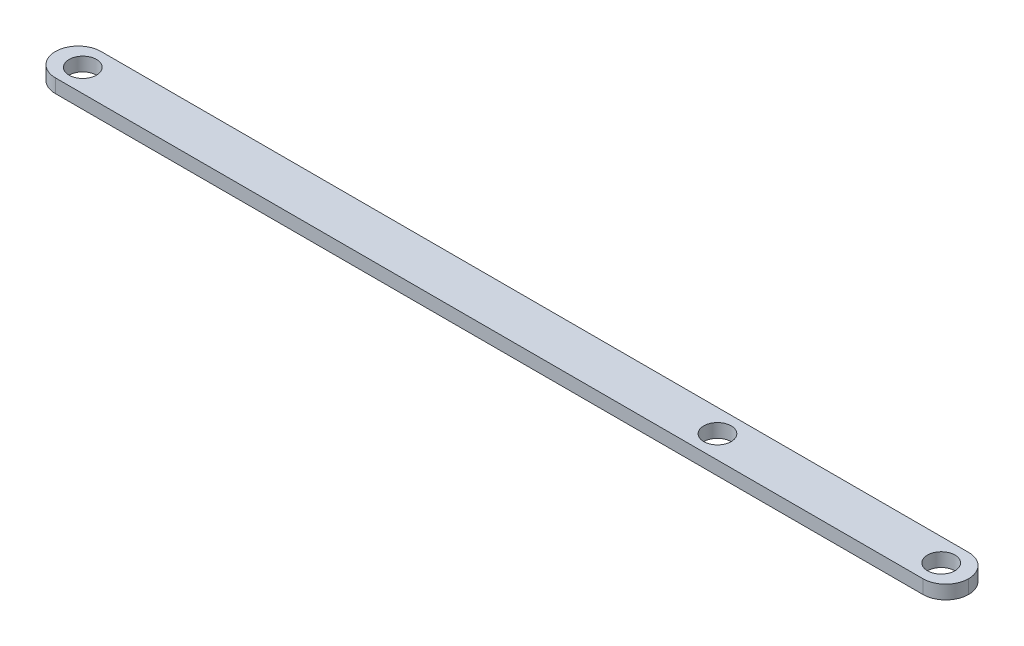
SolidWorks part; units mm, degrees
ref_plane "Front Plane" through (0, 0, 0) normal (0, 0, 1) x (1, 0, 0)
ref_plane "Top Plane" through (0, 0, 0) normal (0, 1, 0) x (1, 0, 0)
ref_plane "Right Plane" through (0, 0, 0) normal (1, 0, 0) x (0, 0, -1)
sketch "Sketch2" plane through (0, 0, 0) normal (0, 1, 0) x (1, 0, 0)
  line L1 (0, 0) -> (200, 0)
  line L2 (0, 0) -> (0, 10)
  line L3 (0, 10) -> (200, 10)
  line L4 (200, 0) -> (200, 10)
  dimension "D1" = 200
  dimension "D2" = 10
extrude "Boss-Extrude1" add sketch "Sketch2" along normal blind 3
sketch "Sketch3" plane through (0, 3, 0) normal (0, 1, 0) x (1, 0, 0)
  line L0 (200, 10) -> (0, 10) construction
  line L1 (0, 10) -> (0, 0) construction
  circle A0 centre (6, 5) radius 3
  dimension "D1" = 5
  dimension "D2" = 6
  dimension "D3" = 6
extrude "Cut-Extrude1" cut sketch "Sketch3" against normal through all
sketch "Sketch4" plane through (0, 3, 0) normal (0, 1, 0) x (1, 0, 0)
  line L0 (200, 10) -> (0, 10) construction
  line L1 (200, 0) -> (200, 10) construction
  circle A0 centre (194, 5) radius 3
  dimension "D1" = 5
  dimension "D3" = 6
  dimension "D2" = 6
extrude "Cut-Extrude2" cut sketch "Sketch4" against normal through all
fillet "Fillet1" radius 5 2 edges at (0, 1.5, -10) (0, 1.5, 0)
fillet "Fillet2" radius 5 2 edges at (200, 1.5, -10) (200, 1.5, 0)
sketch "Sketch5" plane through (0, 3, 0) normal (0, 1, 0) x (1, 0, 0)
  line L0 (5, 0) -> (195, 0) construction
  circle A0 centre (145, 5) radius 3
  point P6 (100, 0)
  dimension "D1" = 145
  dimension "D3" = 6
  dimension "D2" = 5
extrude "Cut-Extrude3" cut sketch "Sketch5" against normal through all
